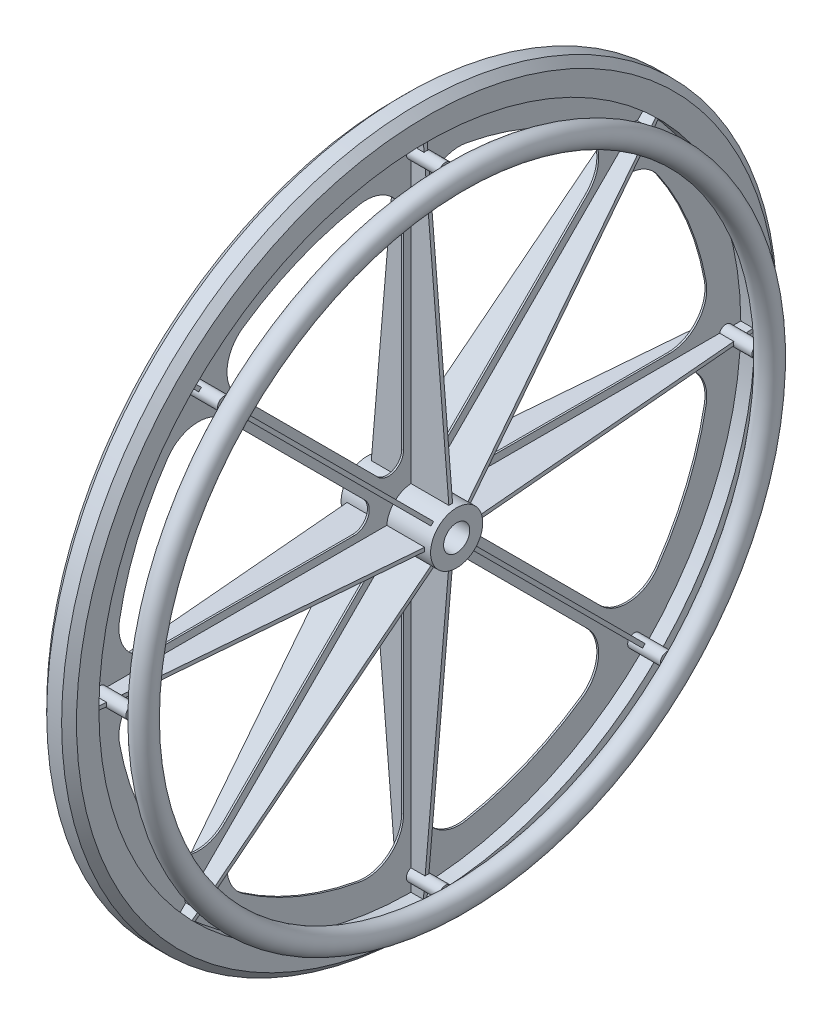
SolidWorks part; units mm, degrees
ref_plane "Front Plane" through (0, 0, 0) normal (0, 0, 1) x (1, 0, 0)
ref_plane "Top Plane" through (0, 0, 0) normal (0, 1, 0) x (1, 0, 0)
ref_plane "Right Plane" through (0, 0, 0) normal (1, 0, 0) x (0, 0, -1)
sketch "Sketch1" plane through (0, 0, 0) normal (1, 0, 0) x (0, 0, -1)
  circle A0 centre (0, 0) radius 22.225
  dimension "D2" = 44.45
extrude "Boss-Extrude1" add sketch "Sketch1" along normal blind 38.1 and the other way blind 38.1
sketch "Sketch2" plane through (0, 0, 0) normal (1, 0, 0) x (0, 0, -1)
  circle A0 centre (0, 0) radius 304.8
  dimension "D1" = 609.6
extrude "Boss-Extrude2" add sketch "Sketch2" along normal blind 0.762 and the other way blind 0.762
sketch "Sketch3" plane through (0, 0, 0) normal (1, 0, 0) x (0, 0, -1)
  circle A0 centre (0, 0) radius 304.8 construction
  circle A1 centre (0, 0) radius 304.8
  circle A2 centre (0, 0) radius 279.4
  dimension "D1" = 25.4
extrude "Boss-Extrude3" add sketch "Sketch3" along normal blind 12.7 and the other way blind 12.7
sketch "Sketch4" plane through (0, 0, 0) normal (1, 0, 0) x (0, 0, -1)
  line L0 (0, 304.8) -> (0, -304.8) construction
  line L1 (-304.8, 0) -> (304.8, 0) construction
  line L2 (-215.5261, -215.5261) -> (215.5261, 215.5261) construction
  line L3 (-215.5261, 215.5261) -> (215.5261, -215.5261) construction
  line L4 (149.0159, 160.2412) -> (29.6178, 40.8431)
  line L5 (7.9375, 218.6778) -> (7.9375, 49.8233)
  circle A0 centre (0, 0) radius 304.8 construction
  circle A1 centre (0, 0) radius 304.8 construction
  arc A2 (45.3571, 249.9174) -> (144.646, 208.7907) centre (0, 0) cw
  arc A3 (29.6178, 40.8431) -> (7.9375, 49.8233) centre (20.6375, 49.8233) cw
  arc A4 (144.646, 208.7907) -> (149.0159, 160.2412) centre (126.5652, 182.6918) cw
  arc A5 (45.3571, 249.9174) -> (7.9375, 218.6778) centre (39.6875, 218.6778) ccw
  dimension "D4" = 50.8
  dimension "D5" = 12.7
  dimension "D6" = 31.75
  dimension "D1" = 45
  dimension "D2" = 15.875
  dimension "D3" = 15.875
extrude "Cut-Extrude1" cut sketch "Sketch4" against normal through all and the other way through all
sketch "Sketch5" plane through (0, 0, 0) normal (0, 1, 0) x (1, 0, 0)
  line L1 (-34.925, -1.5875) -> (34.925, -1.5875)
  line L2 (-34.925, -1.5875) -> (-34.925, 1.5875)
  line L3 (-34.925, 1.5875) -> (34.925, 1.5875)
  line L4 (34.925, -1.5875) -> (34.925, 1.5875)
  line L5 (-34.925, -1.5875) -> (34.925, 1.5875) construction
  line L6 (-34.925, 1.5875) -> (34.925, -1.5875) construction
  line L7 (38.1, -22.225) -> (38.1, 22.225) construction
  point P0 (0, 0)
  dimension "D1" = 3.175
  dimension "D2" = 3.175
ref_plane "Plane1" through (0, 281.94, 0) normal (0, 1, 0) x (-1, 0, 0)
sketch "Sketch6" plane through (0, 281.94, 0) normal (0, 1, 0) x (-1, 0, 0)
  line L1 (11.1125, 1.5875) -> (-11.1125, 1.5875)
  line L2 (11.1125, 1.5875) -> (11.1125, -1.5875)
  line L3 (11.1125, -1.5875) -> (-11.1125, -1.5875)
  line L4 (-11.1125, 1.5875) -> (-11.1125, -1.5875)
  line L5 (11.1125, 1.5875) -> (-11.1125, -1.5875) construction
  line L6 (11.1125, -1.5875) -> (-11.1125, 1.5875) construction
  point P0 (0, 0)
  dimension "D1" = 22.225
  dimension "D2" = 3.175
loft "Loft1" add profiles "Sketch5", "Sketch6"
sketch "Sketch7" plane through (0, 0, 0) normal (1, 0, 0) x (0, 0, -1)
  line L0 (0, 266.7) -> (0, 0) construction
  circle A0 centre (0, 266.7) radius 5.5563
  dimension "D2" = 11.1125
  dimension "D1" = 266.7
extrude "Boss-Extrude5" add sketch "Sketch7" along normal blind 28.575
pattern_circular "CirPattern1" count 8 over 360 about axis through (-38.1, 0, 0) along (1, 0, 0) of "Cut-Extrude1", "Loft1", "Boss-Extrude5"
sketch "Sketch9" plane through (0, 0, 0) normal (1, 0, 0) x (0, 0, -1)
  circle A0 centre (0, 0) radius 11.1125
  dimension "D1" = 22.225
extrude "Cut-Extrude2" cut sketch "Sketch9" against normal through all and the other way through all
sketch "Sketch8" plane through (0, 0, 0) normal (0, 0, 1) x (1, 0, 0)
  line L0 (28.575, 261.1438) -> (28.575, 272.2562) construction
  line L1 (28.575, 261.1438) -> (28.575, 272.2562) construction
  line L2 (28.575, 266.7) -> (38.1, 266.7) construction
  circle A0 centre (38.1, 266.7) radius 9.525
  dimension "D1" = 19.05
revolve "Revolve1" add sketch "Sketch8" angle 360 about axis through (-38.1, 0, 0) along (1, 0, 0)
chamfer "Chamfer1" distance 6.35 angle 45 2 edges at (-12.7, 0, -304.8) (12.7, 0, -304.8)
